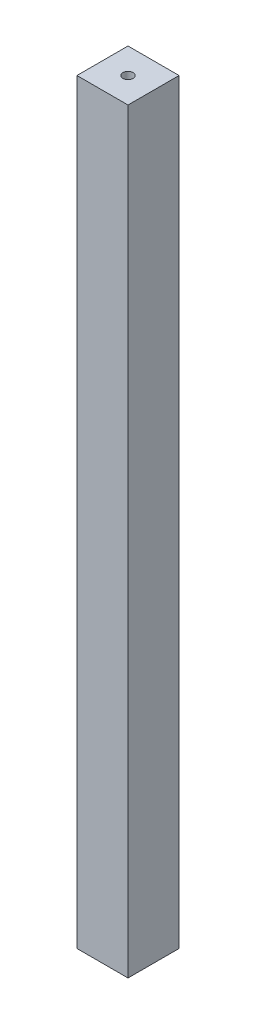
SolidWorks part; units mm, degrees
ref_plane "Front Plane" through (0, 0, 0) normal (0, 0, 1) x (1, 0, 0)
ref_plane "Top Plane" through (0, 0, 0) normal (0, 1, 0) x (1, 0, 0)
ref_plane "Right Plane" through (0, 0, 0) normal (1, 0, 0) x (0, 0, -1)
sketch "Sketch1" plane through (0, 0, 0) normal (0, 1, 0) x (1, 0, 0)
  line L0 (0, -8.25) -> (0, 8.25) construction
  line L1 (-7.5, 7.5) -> (7.5, 7.5)
  line L2 (-7.5, 7.5) -> (-7.5, -7.5)
  line L3 (-7.5, -7.5) -> (7.5, -7.5)
  line L4 (7.5, 7.5) -> (7.5, -7.5)
  line L5 (-8.25, 0) -> (8.25, 0) construction
  circle A0 centre (0, 0) radius 1.5
  dimension "D5" = 3
  dimension "D1" = 15
  dimension "D2" = 15
  dimension "D3" = 7.5
  dimension "D4" = 7.5
extrude "Boss-Extrude1" add sketch "Sketch1" along normal blind 222
